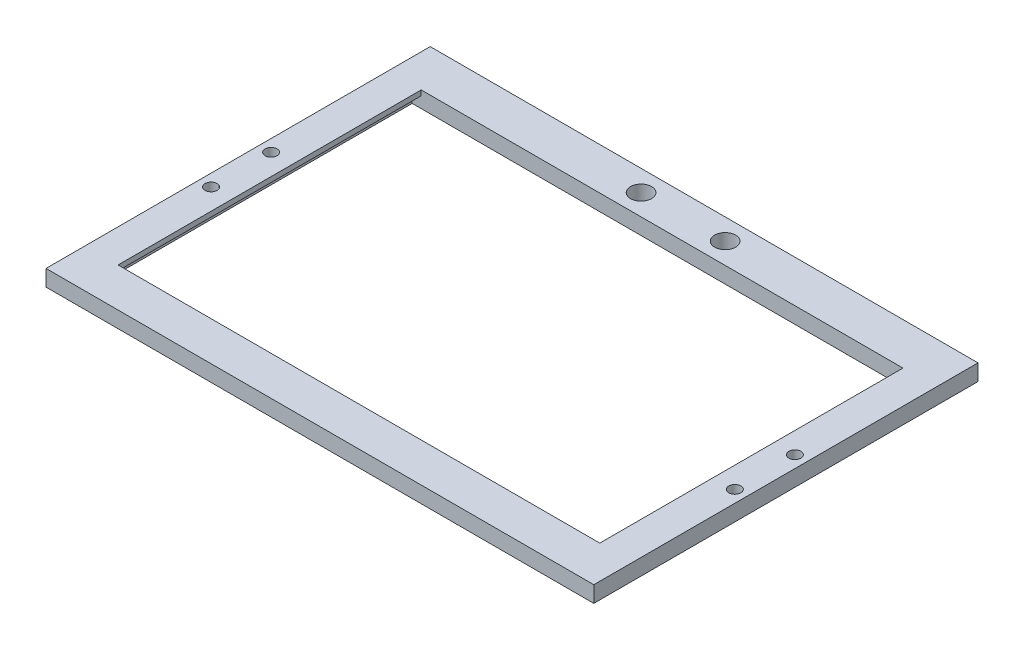
SolidWorks part; units mm, degrees
ref_plane "Front Plane" through (0, 0, 0) normal (0, 0, 1) x (1, 0, 0)
ref_plane "Top Plane" through (0, 0, 0) normal (0, 1, 0) x (1, 0, 0)
ref_plane "Right Plane" through (0, 0, 0) normal (1, 0, 0) x (0, 0, -1)
sketch "Sketch1" plane through (0, 0, 0) normal (0, 1, 0) x (1, 0, 0)
  line L0 (91.25, -61) -> (91.25, 61)
  line L1 (-83.25, -53) -> (83.25, -53)
  line L2 (-83.25, -53) -> (-83.25, 53)
  line L3 (-83.25, 53) -> (83.25, 53)
  line L4 (83.25, -53) -> (83.25, 53)
  line L5 (-83.25, -53) -> (83.25, 53) construction
  line L6 (-83.25, 53) -> (83.25, -53) construction
  line L7 (-91.25, 61) -> (91.25, 61)
  line L8 (-91.25, -61) -> (-91.25, 61)
  line L9 (-91.25, -61) -> (91.25, -61)
  line L10 (-80.25, 53) -> (-80.25, -48)
  line L11 (-83.25, -53) -> (83.25, -53)
  line L12 (-83.25, -53) -> (-83.25, -48)
  line L13 (-83.25, -48) -> (83.25, -48)
  line L14 (83.25, -53) -> (83.25, -48)
  line L15 (80.25, -48) -> (80.25, 53)
  line L16 (-14, 60) -> (14, 60) construction
  line L17 (-91.25, 61) -> (91.25, 61)
  line L18 (-91.25, 61) -> (-91.25, 67)
  line L19 (-91.25, 67) -> (91.25, 67)
  line L20 (91.25, 61) -> (91.25, 67)
  line L21 (0, 0) -> (0, 67) construction
  line L22 (-91.25, 0) -> (91.25, 0) construction
  circle A0 centre (-14, 60) radius 3.5
  circle A1 centre (14, 60) radius 3.5
  circle A2 centre (-87.25, -10) radius 2
  circle A3 centre (-87.25, 10) radius 2
  circle A4 centre (87.25, -10) radius 2
  circle A5 centre (87.25, 10) radius 2
  point P0 (0, 0)
  point P31 (0, 0)
  point P32 (0, 0)
  point P33 (-87.25, 8.4901)
  point P38 (14, 58.4976)
  dimension "D5" = 7
  dimension "D6" = 7
  dimension "D11" = 4
  dimension "D1" = 8
  dimension "D2" = 3
  dimension "D3" = 5
  dimension "D4" = 3
  dimension "D7" = 7
  dimension "D8" = 28
  dimension "D9" = 106
  dimension "D10" = 166.5
  dimension "D12" = 4
  dimension "D13" = 20
extrude "Boss-Extrude1" add sketch "Sketch1" along normal blind 5.4 contours L8 L9 L0 L7 L4 L1 L2 L3 | L2 L13 L10 L3 | L7 L20 L19 L18 A1 A0 | L15 L13 L4 L3 | L13 L15 L3 L10 | L2 L1 L4 L3 region at (0, 0, 58.8048) region at (0, 0, -64.0452) region at (-81.75, 0, -2.5) region at (81.75, 0, -2.5) region at (0, 0, -2.5)
extrude "Cut-Extrude3" cut sketch "Sketch1<4>" along normal through all both and the other way through all contours L13 L15 L3 L10 region at (0, 0, -2.5)
sketch "Sketch1<4>" plane through (0, 0, 0) normal (0, 1, 0) x (1, 0, 0) same geometry as "Sketch1"
extrude "Cut-Extrude4" cut sketch "Sketch1<5>" along normal blind 3.7 contours L13 L2 L1 L4 | L2 L13 L10 L3 | L15 L13 L4 L3 region at (0, 0, 50.5) region at (-81.75, 0, -2.5) region at (81.75, 0, -2.5)
sketch "Sketch1<5>" plane through (0, 0, 0) normal (0, 1, 0) x (1, 0, 0) same geometry as "Sketch1"
